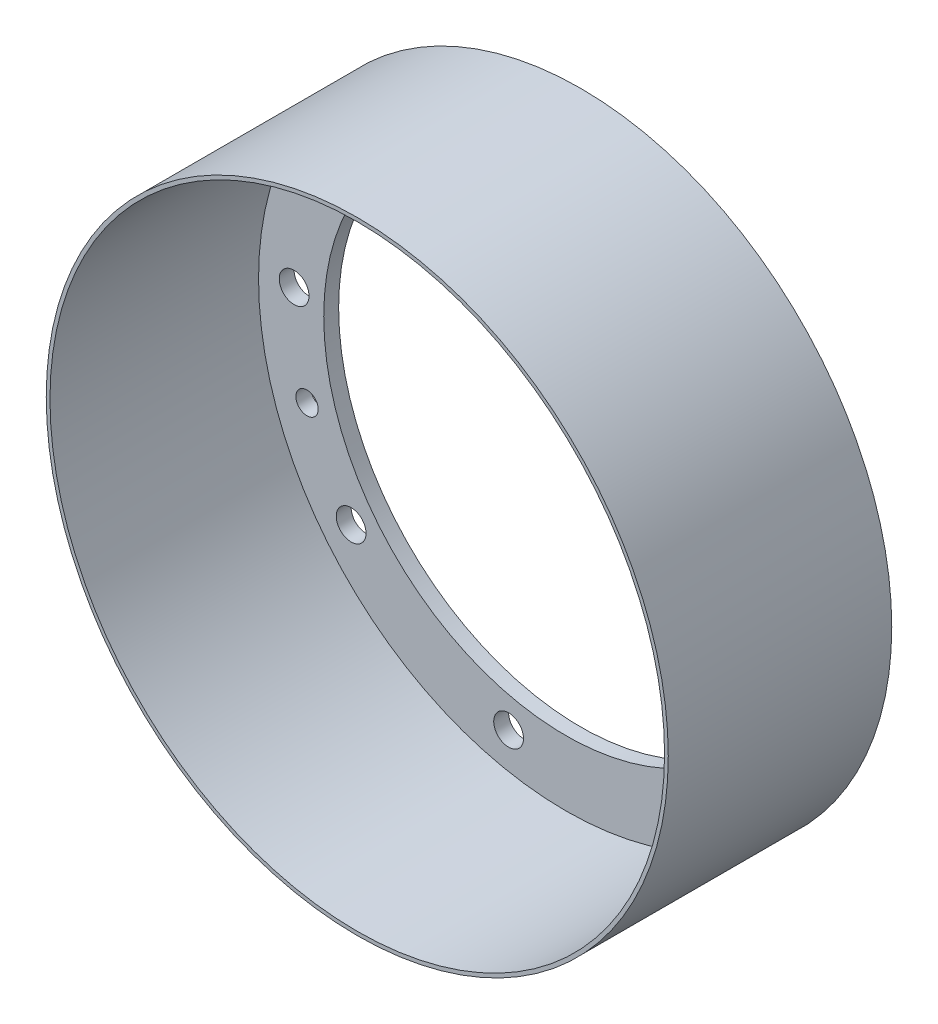
SolidWorks part; units mm, degrees
ref_plane "Front Plane" through (0, 0, 0) normal (0, 0, 1) x (1, 0, 0)
ref_plane "Top Plane" through (0, 0, 0) normal (0, 1, 0) x (1, 0, 0)
ref_plane "Right Plane" through (0, 0, 0) normal (1, 0, 0) x (0, 0, -1)
sketch "Sketch2" plane through (0, 0, 0) normal (0, 0, 1) x (1, 0, 0)
  circle A1 centre (-151.0376, -11.3506) radius 1.5 construction
  circle A2 centre (-149.3061, -23.9081) radius 1.5 construction
  circle A4 centre (-143.3842, -35.1161) radius 1.5 construction
  circle A6 centre (-122.2451, -48.402) radius 1.5 construction
  circle A8 centre (-97.5116, -44.9917) radius 1.5 construction
  circle A9 centre (-87.5023, -37.2134) radius 1.5 construction
  circle A11 centre (-80.7568, -26.4808) radius 1.5 construction
  circle A12 centre (-79.8204, -1.5309) radius 1.5 construction
  circle A15 centre (-95.1406, 18.1837) radius 1.5 construction
  circle A16 centre (-106.8814, 22.963) radius 1.5 construction
  circle A18 centre (-119.5488, 23.4384) radius 1.5 construction
  circle A20 centre (-141.6243, 11.7744) radius 1.5 construction
  circle A21 centre (-114.5633, -12.7195) radius 32.5 construction
  circle A22 centre (-114.5633, -12.7195) radius 39.25 construction
  circle A24 centre (-151.0376, -11.3506) radius 1.5
  circle A25 centre (-149.3061, -23.9081) radius 1.5
  circle A27 centre (-143.3842, -35.1161) radius 1.5
  circle A29 centre (-122.2451, -48.402) radius 1.5
  circle A31 centre (-97.5116, -44.9917) radius 1.5
  circle A32 centre (-87.5023, -37.2134) radius 1.5
  circle A34 centre (-80.7568, -26.4808) radius 1.5
  circle A35 centre (-79.8204, -1.5309) radius 1.5
  circle A38 centre (-95.1406, 18.1837) radius 1.5
  circle A39 centre (-106.8814, 22.963) radius 1.5
  circle A41 centre (-119.5488, 23.4384) radius 1.5
  circle A43 centre (-141.6243, 11.7744) radius 1.5
  circle A44 centre (-114.5633, -12.7195) radius 32.5
  circle A45 centre (-114.5633, -12.7195) radius 39.25
  circle A46 centre (-114.5633, -12.7195) radius 41.25
  circle A47 centre (-114.5633, -12.7195) radius 41.75
  circle A48 centre (-141.6243, 11.7744) radius 2
  circle A49 centre (-119.5488, 23.4384) radius 2
  circle A50 centre (-151.0376, -11.3506) radius 2
  circle A51 centre (-143.3842, -35.1161) radius 2
  circle A52 centre (-122.2451, -48.402) radius 2
  circle A53 centre (-97.5116, -44.9917) radius 2
  circle A54 centre (-80.7568, -26.4808) radius 2
  circle A55 centre (-79.8204, -1.5309) radius 2
  circle A56 centre (-95.1406, 18.1837) radius 2
  dimension "D2" = 0.5
  dimension "D1" = 2
  dimension "D3" = 0.5
extrude "Boss-Extrude1" add sketch "Sketch2" along normal up to surface (28 mm away) contours A47 A46 region at (-156.1952, -12.7195, 0)
sketch "Sketch3" plane through (0, 0, 0) normal (1, 0, 0) x (0, 0, -1)
  line L0 (-36.15, -6.5468) -> (-30.65, -6.5468) construction
  line L1 (-30.65, -21.5363) -> (-30.65, -6.5468) construction
  line L2 (-36.15, -21.5363) -> (-30.65, -21.5363) construction
  line L3 (-36.15, -21.5363) -> (-36.15, -6.5468) construction
  line L4 (-36.15, -6.5468) -> (-30.65, -6.5468)
  line L5 (-30.65, -21.5363) -> (-30.65, -6.5468)
  line L6 (-36.15, -21.5363) -> (-30.65, -21.5363)
  line L7 (-36.15, -21.5363) -> (-36.15, -6.5468)
  line L8 (-38.15, -4.5468) -> (-28.65, -4.5468)
  line L9 (-28.65, -23.5363) -> (-28.65, -4.5468)
  line L10 (-38.15, -23.5363) -> (-28.65, -23.5363)
  line L11 (-38.15, -23.5363) -> (-38.15, -4.5468)
  dimension "D1" = 2
extrude "Cut-Extrude1" [suppressed] cut sketch "Sketch3" against normal through all contours L7 L6 L5 L4 | L11 L10 L9 L8 L6 L7 L4 L5
extrude "Boss-Extrude2" add sketch "Sketch2<3>" against normal blind 2 contours A45 A24 A25 A27 A29 A31 A32 A34 A35 A38 A39 A41 A43 A44 | A46 A45 | A47 A46 region at (-152.7031, -12.7195, 0) region at (-154.6465, -12.7195, 0) region at (-156.1952, -12.7195, 0)
sketch "Sketch2<3>" plane through (0, 0, 0) normal (0, 0, 1) x (1, 0, 0) same geometry as "Sketch2"
ref_plane "Plane1" through (0, 0, 0) normal (0, 0, 1) x (1, 0, 0)
